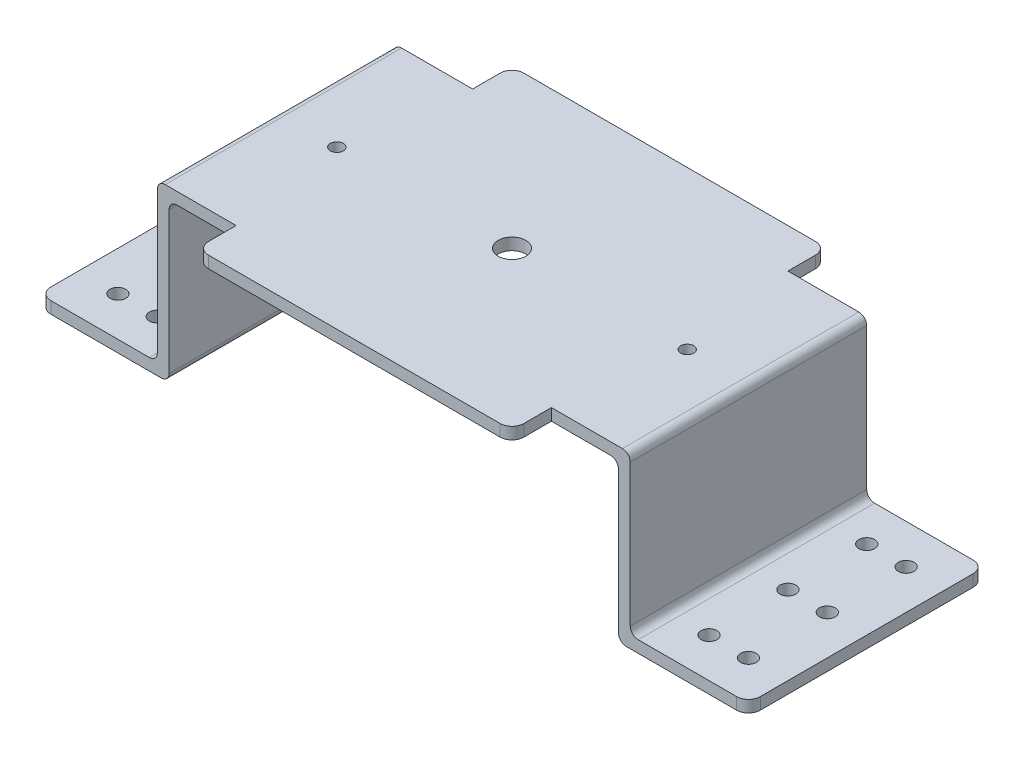
SolidWorks part; units mm, degrees
ref_plane "Front" through (0, 0, 0) normal (0, 0, 1) x (1, 0, 0)
ref_plane "Top" through (0, 0, 0) normal (0, 1, 0) x (1, 0, 0)
ref_plane "Right" through (0, 0, 0) normal (1, 0, 0) x (0, 0, -1)
sketch "草图1" plane through (0, 0, 0) normal (0, 1, 0) x (1, 0, 0)
  line L1 (-60, 30) -> (60, 30)
  line L2 (-60, 30) -> (-60, -30)
  line L3 (-60, -30) -> (60, -30)
  line L4 (60, 30) -> (60, -30)
  line L5 (-60, 30) -> (60, -30) construction
  line L6 (-60, -30) -> (60, 30) construction
  point P0 (0, 0)
  dimension "D1" = 60
  dimension "D2" = 120
extrude "凸台-拉伸1" add sketch "草图1" along normal blind 3 contours L1 L4 L3 L2
sketch "草图2" plane through (0, 0, 0) normal (0, -1, 0) x (1, 0, 0)
  line L0 (-60, -30) -> (60, -30) construction
  line L1 (-60, 30) -> (-57, 30)
  line L2 (-60, 30) -> (-60, -30)
  line L3 (-60, -30) -> (-57, -30)
  line L4 (-57, 30) -> (-57, -30)
  dimension "D1" = 3
extrude "凸台-拉伸2" add sketch "草图2" along normal blind 40
sketch "草图3" plane through (-60, 0, 0) normal (-1, 0, 0) x (0, 0, 1)
  line L0 (30, 3) -> (30, -40) construction
  line L1 (-30, -40) -> (30, -40)
  line L2 (-30, -40) -> (-30, -37)
  line L3 (-30, -37) -> (30, -37)
  line L4 (30, -40) -> (30, -37)
  dimension "D1" = 3
extrude "凸台-拉伸3" add sketch "草图3" along normal blind 30
sketch "草图4" plane through (0, -37, 0) normal (0, 1, 0) x (1, 0, 0)
  line L0 (-90, -30) -> (-60, -30) construction
  line L1 (0, -50) -> (0, 50) construction
  circle A0 centre (-70, -20) radius 2
  dimension "D1" = 4
  dimension "D2" = 10
  dimension "D3" = 70
extrude "切除-拉伸1" cut sketch "草图4" against normal blind 3
pattern_linear "阵列(线性)1" count 3 spacing 20 along (0, 0, -1) count 2 spacing 10 along (-1, 0, 0) of "切除-拉伸1"
mirror "镜向1" about plane through (0, 0, 0) normal (1, 0, 0) of "阵列(线性)1", "凸台-拉伸3", "凸台-拉伸2"
sketch "草图5" plane through (0, 3, 0) normal (0, 1, 0) x (1, 0, 0)
  circle A0 centre (0, 0) radius 3.5
  dimension "D1" = 7
extrude "切除-拉伸2" cut sketch "草图5" against normal blind 3
sketch "草图6" plane through (0, 3, 0) normal (0, 1, 0) x (1, 0, 0)
  circle A0 centre (44.45, 0) radius 1.5
  circle A1 centre (0, 0) radius 3.5 construction
  dimension "D1" = 3
  dimension "D2" = 44.45
extrude "切除-拉伸3" cut sketch "草图6" against normal blind 3
mirror "镜向2" about plane through (0, 0, 0) normal (1, 0, 0) of "切除-拉伸3"
sketch "草图7" plane through (0, 3, 0) normal (0, 1, 0) x (1, 0, 0)
  line L0 (-60, 30) -> (60, 30) construction
  line L1 (-40, 30) -> (40, 30)
  line L2 (-40, 30) -> (-40, 40)
  line L3 (-40, 40) -> (40, 40)
  line L4 (40, 30) -> (40, 40)
  circle A0 centre (0, 0) radius 3.5 construction
  dimension "D1" = 40
  dimension "D2" = 40
  dimension "D3" = 40
extrude "凸台-拉伸4" add sketch "草图7" against normal blind 3
mirror "镜向3" about plane through (0, 0, 0) normal (0, 0, 1) of "凸台-拉伸4"
fillet "圆角1" radius 3 1 edges at (-40, 1.5, 40)
fillet "圆角2" radius 3 3 edges at (40, 1.5, 40) (40, 1.5, -40) (-40, 1.5, -40)
fillet "圆角3" radius 2 2 edges at (-57, 0, 0) (-60, 3, 0)
fillet "圆角4" radius 2 6 edges at (-57, -40, 0) (-60, -37, 0) (60, -37, 0) (57, -40, 0) (57, 0, 0) (60, 3, 0)
fillet "圆角5" radius 3 4 edges at (90, -38.5, -30) (90, -38.5, 30) (-90, -38.5, -30) (-90, -38.5, 30)
hole_wizard "M4 螺纹孔1" positions "草图14" profile "草图15" tap size "M4" standard "GB" end condition through all
sketch "草图14" plane through (0, 3, 0) normal (0, 1, 0) x (1, 0, 0)
  point P0 (44.45, 0)
  point P3 (-44.45, 0)
sketch "草图15" plane through (44.45, 3, 0) normal (1, 0, 0) x (0, 0, 1)
  line L0 (0, 0) -> (0, 43)
  line L1 (0, 43) -> (1.65, 43)
  line L2 (1.65, 43) -> (1.65, 0)
  line L5 (1.65, 0) -> (0, 0)
  line L11 (0, -6.35) -> (0, 107.95) construction
  dimension "通孔螺纹孔钻头直径" = 3.3
  dimension "通孔螺纹孔钻头深度" = 43
cosmetic thread "孔螺蚊线2" parameters "D2"=4
cosmetic thread "孔螺蚊线3" parameters "D2"=4
